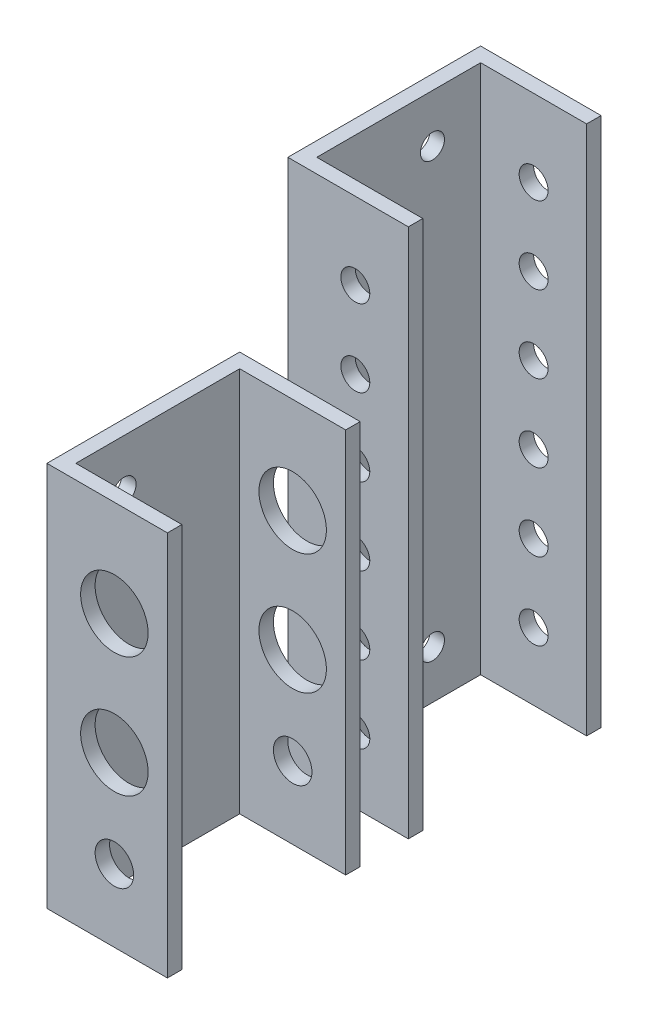
SolidWorks part; units mm, degrees
ref_plane "정면" through (0, 0, 0) normal (0, 0, 1) x (1, 0, 0)
ref_plane "윗면" through (0, 0, 0) normal (0, 1, 0) x (1, 0, 0)
ref_plane "우측면" through (0, 0, 0) normal (1, 0, 0) x (0, 0, -1)
sketch "스케치1" plane through (0, 0, 0) normal (0, 1, 0) x (1, 0, 0)
  line L0 (0, 0) -> (25, 0)
  line L1 (25, 0) -> (25, 3)
  line L2 (25, 3) -> (3, 3)
  line L3 (3, 3) -> (3, 37)
  line L4 (3, 37) -> (25, 37)
  line L5 (25, 37) -> (25, 40)
  line L6 (25, 40) -> (0, 40)
  line L7 (0, 40) -> (0, 0)
  line L8 (0, 45) -> (63.5712, 45) construction
  line L9 (25, 90) -> (25, 87)
  line L10 (0, 90) -> (25, 90)
  line L11 (25, 87) -> (3, 87)
  line L12 (3, 87) -> (3, 53)
  line L13 (0, 50) -> (0, 90)
  line L14 (3, 53) -> (25, 53)
  line L15 (25, 50) -> (0, 50)
  line L16 (25, 53) -> (25, 50)
  dimension "D1" = 3
  dimension "D2" = 3
  dimension "D3" = 40
  dimension "D4" = 25
  dimension "D5" = 3
  dimension "D6" = 25
  dimension "D7" = 5
extrude "보스-돌출2" add sketch "스케치1" along normal blind 80 contours L6 L7 L0 L1 L2 L3 L4 L5
extrude "보스-돌출3" add sketch "스케치1<4>" along normal blind 110 separate body contours L12 L14 L16 L15 L13 L10 L9 L11
sketch "스케치1<4>" plane through (0, 0, 0) normal (0, 1, 0) x (1, 0, 0) same geometry as "스케치1"
sketch "스케치6" plane through (0, 0, 0) normal (0, 0, 1) x (1, 0, 0)
  line L0 (25, 80) -> (25, 0) construction
  line L1 (14, 99.7025) -> (14, -7.7349) construction
  line L3 (0, 80) -> (25, 80) construction
  line L4 (0, 0) -> (25, 0) construction
  circle A0 centre (14, 60) radius 7
  circle A1 centre (14, 35) radius 7
  circle A2 centre (14, 15) radius 4
  point P10 (0, 0)
  point P11 (0, 0)
  point P12 (14, 59.6013)
  point P13 (0, 0)
  point P14 (0, 0)
  point P17 (0, 0)
  dimension "D1" = 8
  dimension "D2" = 14
  dimension "D3" = 14
  dimension "D4" = 11
  dimension "D5" = 25
  dimension "D6" = 20
  dimension "D7" = 15
extrude "컷-돌출2" cut sketch "스케치6" against normal blind 40
sketch "스케치7" plane through (0, 0, -90) normal (0, 0, -1) x (-1, 0, 0)
  line L0 (-14, 113.3101) -> (-14, -2.2216) construction
  line L1 (-25, 110) -> (-25, 0) construction
  line L2 (0, 110) -> (-25, 110) construction
  line L3 (0, 0) -> (-25, 0) construction
  circle A0 centre (-14, 94) radius 3
  circle A1 centre (-14, 78) radius 3
  circle A2 centre (-14, 62) radius 3
  circle A3 centre (-14, 46) radius 3
  circle A4 centre (-14, 30) radius 3
  circle A5 centre (-14, 14) radius 3
  point P18 (-14, 4.7585)
  point P19 (-14, 17.2183)
  point P20 (-14, 62)
  point P21 (-13.7447, 62)
  point P22 (0, 0)
  point P23 (-13.7447, 62)
  point P24 (-13.7447, 62)
  point P25 (-13.7447, 62)
  point P26 (-14, 42.9142)
  point P29 (-14, 94)
  point P30 (-14, 78)
  dimension "D1" = 6
  dimension "D2" = 6
  dimension "D3" = 6
  dimension "D4" = 6
  dimension "D5" = 6
  dimension "D6" = 6
  dimension "D7" = 11
  dimension "D8" = 16
  dimension "D9" = 16
  dimension "D10" = 16
  dimension "D11" = 16
  dimension "D12" = 16
  dimension "D13" = 16
  dimension "D14" = 14
extrude "컷-돌출3" cut sketch "스케치7" against normal blind 40
sketch "스케치8" plane through (3, 0, 0) normal (1, 0, 0) x (0, 0, -1)
  line L0 (87, 110) -> (53, 110) construction
  line L1 (90, 110) -> (90, 0) construction
  line L2 (87, 0) -> (53, 0) construction
  line L3 (3, 0) -> (37, 0) construction
  line L4 (0, 80) -> (0, 0) construction
  line L5 (3, 80) -> (37, 80) construction
  circle A0 centre (77, 100) radius 2.5
  circle A1 centre (77, 10) radius 2.5
  circle A2 centre (13, 10) radius 2.5
  circle A3 centre (13, 70) radius 2.5
  dimension "D1" = 5
  dimension "D2" = 5
  dimension "D3" = 5
  dimension "D4" = 5
  dimension "D5" = 10
  dimension "D6" = 13
  dimension "D7" = 13
  dimension "D8" = 10
  dimension "D9" = 10
  dimension "D10" = 13
  dimension "D11" = 10
  dimension "D12" = 13
extrude "컷-돌출4" cut sketch "스케치8" against normal blind 40 contours A2 | A3 | A0 | A1
